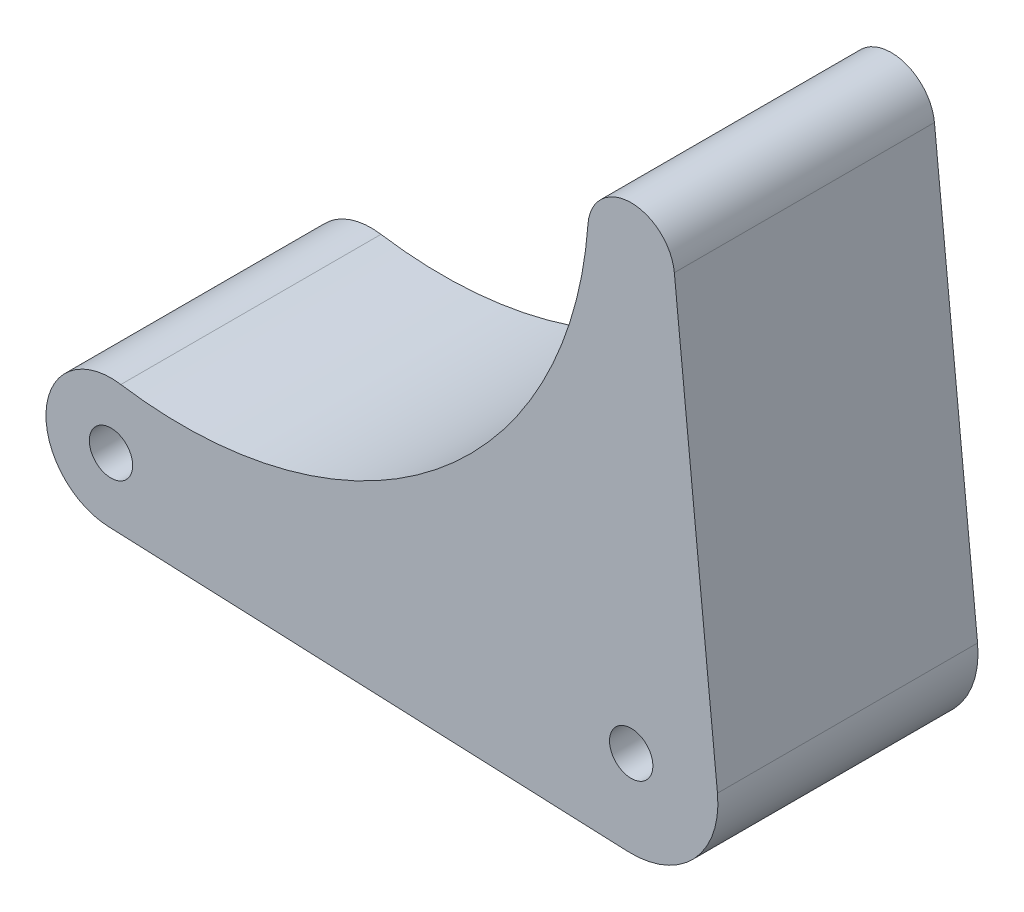
SolidWorks part; units mm, degrees
ref_plane "Front Plane" through (0, 0, 0) normal (0, 0, 1) x (1, 0, 0)
ref_plane "Top Plane" through (0, 0, 0) normal (0, 1, 0) x (1, 0, 0)
ref_plane "Right Plane" through (0, 0, 0) normal (1, 0, 0) x (0, 0, -1)
sketch "Sketch1" plane through (0, 0, 0) normal (0, 0, 1) x (1, 0, 0)
  line L0 (-76.5969, -9.5167) -> (-0.5292, -12.689)
  line L1 (6.3182, 64.135) -> (12.6363, 1.27)
  circle A0 centre (-76.2, 0) radius 3.175
  circle A1 centre (0, 0) radius 3.175
  circle A2 centre (-76.2, 0) radius 9.525 construction
  arc A3 (-0.5292, -12.689) -> (12.6363, 1.27) centre (0, 0) ccw
  arc A4 (-74.754, 9.4146) -> (-76.5969, -9.5167) centre (-76.2, 0) ccw
  arc A5 (6.3182, 64.135) -> (-6.3334, 63.959) centre (0, 63.5) ccw
  arc A6 (-74.754, 9.4146) -> (-6.3334, 63.959) centre (-65.7156, 68.2625) ccw
  dimension "D1" = 76.2
  dimension "D2" = 6.35
  dimension "D3" = 6.35
  dimension "D4" = 19.05
  dimension "D5" = 12.7
  dimension "D6" = 6.35
  dimension "D7" = 63.5
extrude "Boss-Extrude1" add sketch "Sketch1" along normal blind 38.1
